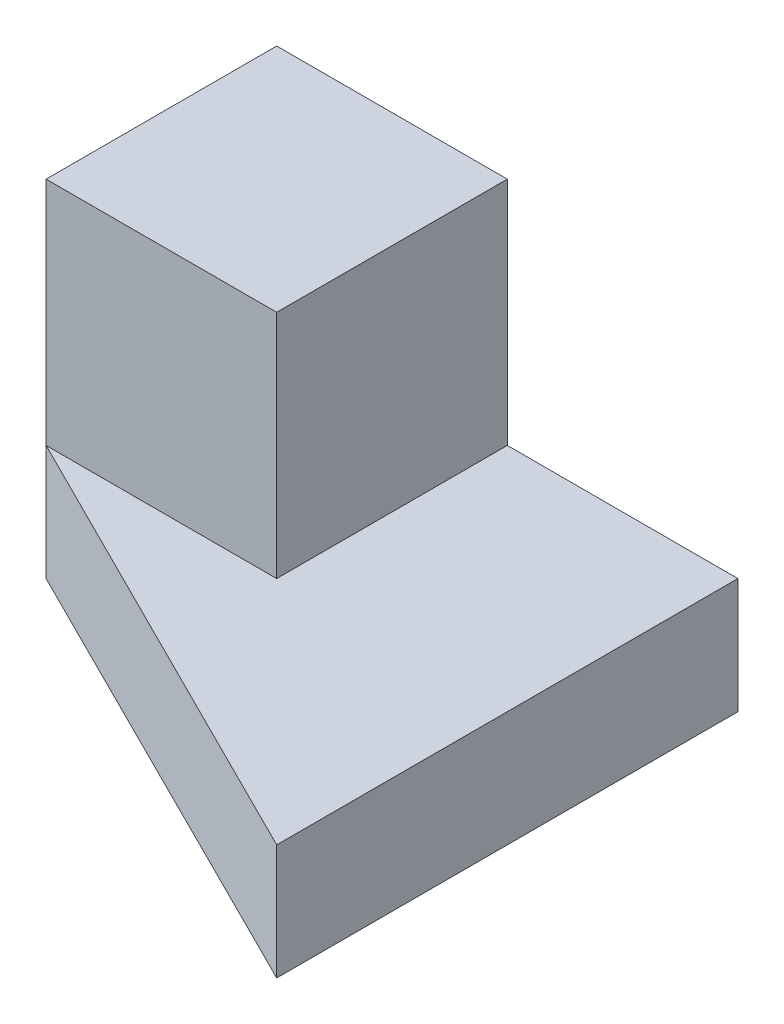
SolidWorks part; units mm, degrees
ref_plane "Front Plane" through (0, 0, 0) normal (0, 0, 1) x (1, 0, 0)
ref_plane "Top Plane" through (0, 0, 0) normal (0, 1, 0) x (1, 0, 0)
ref_plane "Right Plane" through (0, 0, 0) normal (1, 0, 0) x (0, 0, -1)
sketch "Sketch2" plane through (0, 0, 0) normal (0, 1, 0) x (1, 0, 0)
  line L0 (0, 0) -> (0, 40)
  line L1 (0, 40) -> (-40, 40)
  line L2 (-40, 40) -> (-40, 20)
  line L3 (-40, 20) -> (0, 0)
  line L4 (-40, 20) -> (-20, 20)
  line L5 (-20, 20) -> (-20, 40)
  dimension "D1" = 40
  dimension "D2" = 40
  dimension "D3" = 20
  dimension "D4" = 20
extrude "Boss-Extrude1" add sketch "Sketch2" along normal blind 10 contours L5 L4 L3 L0 L1 region at (-11.6667, 0, -21.6667)
extrude "Boss-Extrude2" add sketch "Sketch2<3>" along normal blind 30 contours L4 L5 L1 L2 region at (-30, 0, -30)
sketch "Sketch2<3>" plane through (0, 0, 0) normal (0, 1, 0) x (1, 0, 0) same geometry as "Sketch2"
